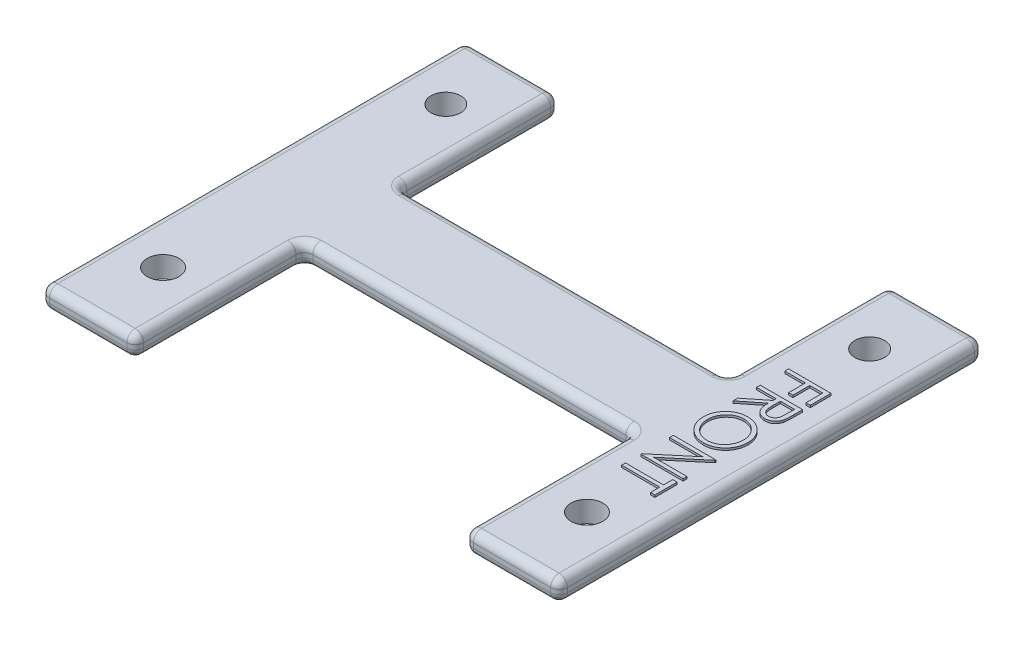
SolidWorks part; units mm, degrees
material "Plain Carbon Steel"
ref_plane "Front Plane" through (0, 0, 0) normal (0, 0, 1) x (1, 0, 0)
ref_plane "Top Plane" through (0, 0, 0) normal (0, 1, 0) x (1, 0, 0)
ref_plane "Right Plane" through (0, 0, 0) normal (1, 0, 0) x (0, 0, -1)
sketch "Sketch1" plane through (0, 0, 0) normal (0, 1, 0) x (1, 0, 0)
  line L10 (-310.388, 248.768) -> (-197.612, 248.768)
  line L11 (0, -89.814) -> (0, 79.35) construction
  line L15 (-310.388, 248.768) -> (-310.388, -259.232)
  line L16 (-310.388, -259.232) -> (-197.612, -259.232)
  line L21 (-197.612, 79.35) -> (-197.612, 248.768)
  line L23 (-197.612, -89.814) -> (-197.612, -259.232)
  line L25 (310.388, -259.232) -> (197.612, -259.232)
  line L26 (197.612, -89.814) -> (197.612, -259.232)
  line L27 (197.612, 79.35) -> (197.612, 248.768)
  line L28 (310.388, 248.768) -> (197.612, 248.768)
  line L29 (310.388, 248.768) -> (310.388, -259.232)
  line L33 (-197.612, -89.814) -> (-197.612, -56.388)
  line L34 (-197.612, -56.388) -> (197.612, -56.388)
  line L35 (197.612, -56.388) -> (197.612, -89.814)
  line L37 (-197.612, 79.35) -> (-197.612, 56.388)
  line L38 (-197.612, 56.388) -> (197.612, 56.388)
  line L39 (197.612, 56.388) -> (197.612, 79.35)
  point P0 (0, 0)
  point P16 (0, 79.35)
extrude "Boss-Extrude4" add sketch "Sketch1" against normal mid plane 25.4
fillet "Fillet1" radius 10 9 edges at (197.612, -12.7, 157.81) (197.612, 12.7, 157.81) (197.612, 0, 56.388) (0, -12.7, 56.388) (0, 12.7, 56.388) (-197.612, 0, 56.388) (-197.612, -12.7, 157.81) (-197.612, 0, 259.232) (-197.612, 12.7, 157.81)
fillet "Fillet2" radius 10 5 edges at (-200.5409, -9.7711, 256.303) (-310.388, 0, 259.232) (-259, 12.7, 259.232) (-259, -12.7, 259.232) (-200.5409, 9.7711, 256.303)
fillet "Fillet3" radius 10 6 edges at (259, 12.7, 259.232) (310.388, 0, 259.232) (259, -12.7, 259.232) (200.5409, -9.7711, 259.232) (197.612, 0, 259.232) (200.5409, 9.7711, 259.232)
fillet "Fillet4" radius 10 24 edges at (-307.4591, 9.7711, 256.303) (-307.4591, -9.7711, 256.303) (307.4591, -9.7711, 256.303) (-310.388, 12.7, 0.232) (-310.388, -12.7, 0.232) (-310.388, 0, -248.768) (-254, -12.7, -248.768) (-254, 12.7, -248.768) (-197.612, 0, -248.768) (-197.612, -12.7, -152.578) (-197.612, 12.7, -152.578) (-197.612, 0, -56.388) (0, -12.7, -56.388) (0, 12.7, -56.388) (197.612, 0, -56.388) (197.612, -12.7, -152.578) (197.612, 12.7, -152.578) (197.612, 0, -248.768) (254, -12.7, -248.768) (254, 12.7, -248.768) (310.388, 0, -248.768) (310.388, -12.7, 0.232) (310.388, 12.7, 0.232) (307.4591, 9.7711, 256.303)
sketch "Sketch2" plane through (0, 0, 0) normal (0, 1, 0) x (1, 0, 0)
  line L3 (0, -13.97) -> (0, 13.97) construction
  circle A0 centre (-254, 169.418) radius 17.78
  circle A1 centre (-254, -169.418) radius 19.05
  circle A2 centre (254, -169.418) radius 19.05
  circle A3 centre (254, 169.418) radius 17.78
extrude "Cut-Extrude1" cut sketch "Sketch2" against normal mid plane 91.44
sketch "Sketch3" plane through (0, 12.7, 0) normal (0, 1, 0) x (1, 0, 0)
  line L1 (228.567, 238.768) -> (228.567, -249.232) construction
  line L2 (300.388, 238.768) -> (207.612, 238.768) construction
  line L3 (207.612, -249.232) -> (300.388, -249.232) construction
  text T0 "FRONT" font "Century Gothic" height 50.8
extrude "Boss-Extrude5" add sketch "Sketch3" along normal blind 2.54
